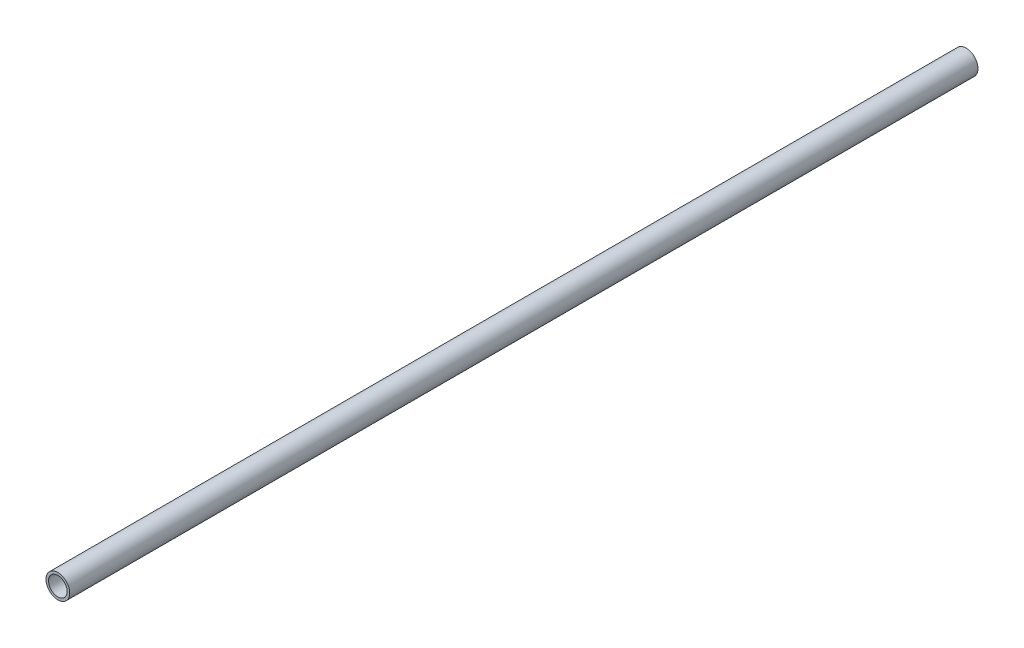
SolidWorks part; units mm, degrees
material "AISI 1020"
ref_plane "Front Plane" through (0, 0, 0) normal (0, 0, 1) x (1, 0, 0)
ref_plane "Top Plane" through (0, 0, 0) normal (0, 1, 0) x (1, 0, 0)
ref_plane "Right Plane" through (0, 0, 0) normal (1, 0, 0) x (0, 0, -1)
sketch "Sketch1" plane through (0, 0, 0) normal (0, 0, 1) x (1, 0, 0)
  circle A0 centre (0, 0) radius 11.11
  circle A1 centre (0, 0) radius 8.73
  dimension "D1" = 22.22
  dimension "D2" = 2.38
extrude "Boss-Extrude1" add sketch "Sketch1" along normal blind 850
ref_plane "Plane1" through (0, 0, 650) normal (0, 0, 1) x (1, 0, 0)
ref_plane "Plane2" through (0, 0, 200) normal (0, 0, -1) x (-1, 0, 0)
sketch "Sketch2" plane through (0, 0, 650) normal (0, 0, 1) x (1, 0, 0)
  circle A0 centre (0, 0) radius 11.6244
  circle A1 centre (0, 0) radius 11.1
  circle A2 centre (0, 0) radius 11.11 construction
  dimension "D1" = 0.01
extrude "Cut-Extrude1" [suppressed] cut sketch "Sketch2" against normal blind 1
pattern_linear "LPattern1" [suppressed] count 2 spacing 500 of bodies 102
sketch "Sketch3" plane through (0, 0, 850) normal (0, 0, 1) x (1, 0, 0)
  line L0 (-10.7284, 2.4744) -> (-12.3297, 2.4744)
  line L1 (-12.3297, 2.4744) -> (-10.7284, 2.4744)
  line L2 (10.7284, 2.4744) -> (12.3297, 2.4744)
  arc A0 (12.3297, 2.4744) -> (-12.3297, 2.4744) centre (0, 0) ccw
  arc A1 (10.7284, 2.4744) -> (-10.7284, 2.4744) centre (0, 0) ccw
  circle A2 centre (0, 0) radius 11.11 construction
  circle M2 centre (0, 0) radius 11.11
  dimension "D1" = 0.1
extrude "Cut-Extrude6" [suppressed] cut sketch "Sketch3" against normal blind 200 from offset 300 contours L2 A0 L0 M2 | A1 L2 L0 M2 offset against normal yes
